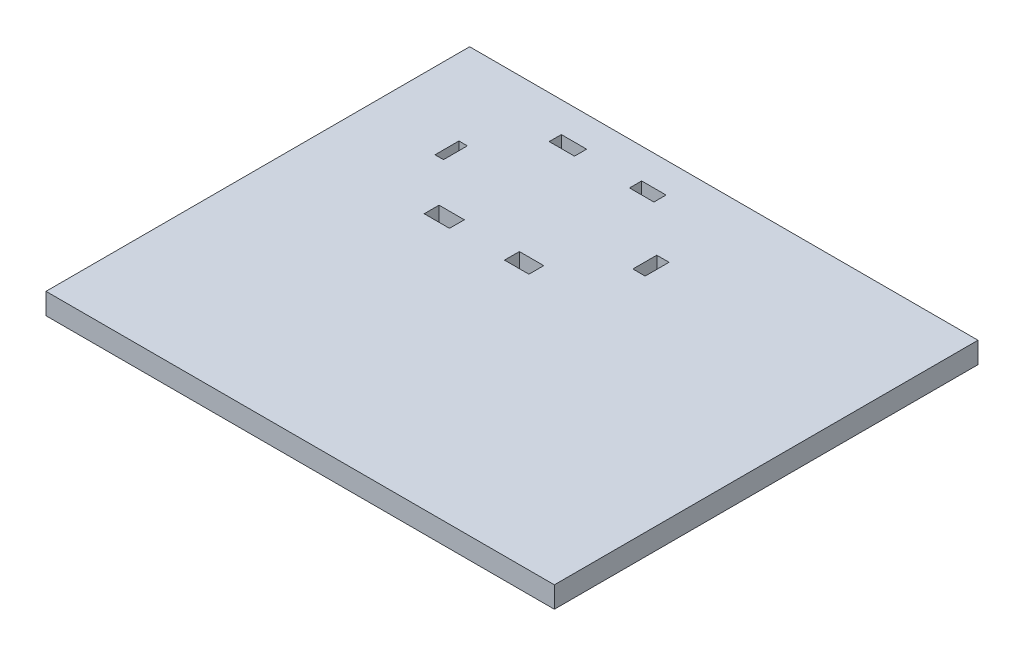
SolidWorks part; units mm, degrees
ref_plane "Front Plane" through (0, 0, 0) normal (0, 0, 1) x (1, 0, 0)
ref_plane "Top Plane" through (0, 0, 0) normal (0, 1, 0) x (1, 0, 0)
ref_plane "Right Plane" through (0, 0, 0) normal (1, 0, 0) x (0, 0, -1)
sketch "Sketch1" plane through (0, 0, 0) normal (0, 1, 0) x (1, 0, 0)
  line L1 (-68.809, 53.869) -> (51.191, 53.869)
  line L2 (-68.809, 53.869) -> (-68.809, -46.131)
  line L3 (-68.809, -46.131) -> (51.191, -46.131)
  line L4 (51.191, 53.869) -> (51.191, -46.131)
  dimension "D1" = 100
  dimension "D2" = 120
extrude "Boss-Extrude1" add sketch "Sketch1" along normal blind 5
sketch "Sketch2" plane through (0, 5, 0) normal (0, 1, 0) x (1, 0, 0)
  line L0 (-90.0225, 3.869) -> (70.1864, 3.869) construction
  line L1 (51.191, -46.131) -> (51.191, 53.869) construction
  line L2 (-68.809, 53.869) -> (-68.809, -46.131) construction
  line L3 (-48.809, 43.869) -> (-4.109, 43.869) construction
  line L4 (-48.809, 43.869) -> (-48.809, 17.869) construction
  line L5 (-48.809, 17.869) -> (-4.109, 17.869) construction
  line L6 (-4.109, 43.869) -> (-4.109, 17.869) construction
  line L7 (51.191, 53.869) -> (-68.809, 53.869) construction
  line L9 (-40.0318, 17.869) -> (-34.0603, 17.869)
  line L10 (-40.0318, 17.869) -> (-40.0318, 14.362)
  line L11 (-40.0318, 14.362) -> (-34.0603, 14.362)
  line L12 (-34.0603, 17.869) -> (-34.0603, 14.362)
  line L13 (-48.809, 33.339) -> (-50.8073, 33.339)
  line L14 (-48.809, 33.339) -> (-48.809, 27.6971)
  line L15 (-48.809, 27.6971) -> (-50.8073, 27.6971)
  line L16 (-50.8073, 33.339) -> (-50.8073, 27.6971)
  line L17 (-21.0703, 17.869) -> (-15.3109, 17.869)
  line L18 (-21.0703, 17.869) -> (-21.0703, 14.362)
  line L19 (-21.0703, 14.362) -> (-15.3109, 14.362)
  line L20 (-15.3109, 17.869) -> (-15.3109, 14.362)
  line L21 (-40.0318, 43.869) -> (-34.0603, 43.869)
  line L22 (-40.0318, 43.869) -> (-40.0318, 46.7383)
  line L23 (-40.0318, 46.7383) -> (-34.0603, 46.7383)
  line L24 (-34.0603, 43.869) -> (-34.0603, 46.7383)
  line L25 (-21.0703, 43.869) -> (-15.3109, 43.869)
  line L26 (-21.0703, 43.869) -> (-21.0703, 46.7383)
  line L27 (-21.0703, 46.7383) -> (-15.3109, 46.7383)
  line L28 (-15.3109, 43.869) -> (-15.3109, 46.7383)
  line L29 (-4.109, 33.339) -> (-1.2064, 33.339)
  line L30 (-4.109, 33.339) -> (-4.109, 27.6971)
  line L31 (-4.109, 27.6971) -> (-1.2064, 27.6971)
  line L32 (-1.2064, 33.339) -> (-1.2064, 27.6971)
  point P4 (51.191, 3.869)
  dimension "D1" = 44.7
  dimension "D2" = 26
  dimension "D3" = 20
  dimension "D4" = 10
extrude "Cut-Extrude3" cut sketch "Sketch2" against normal up to next
